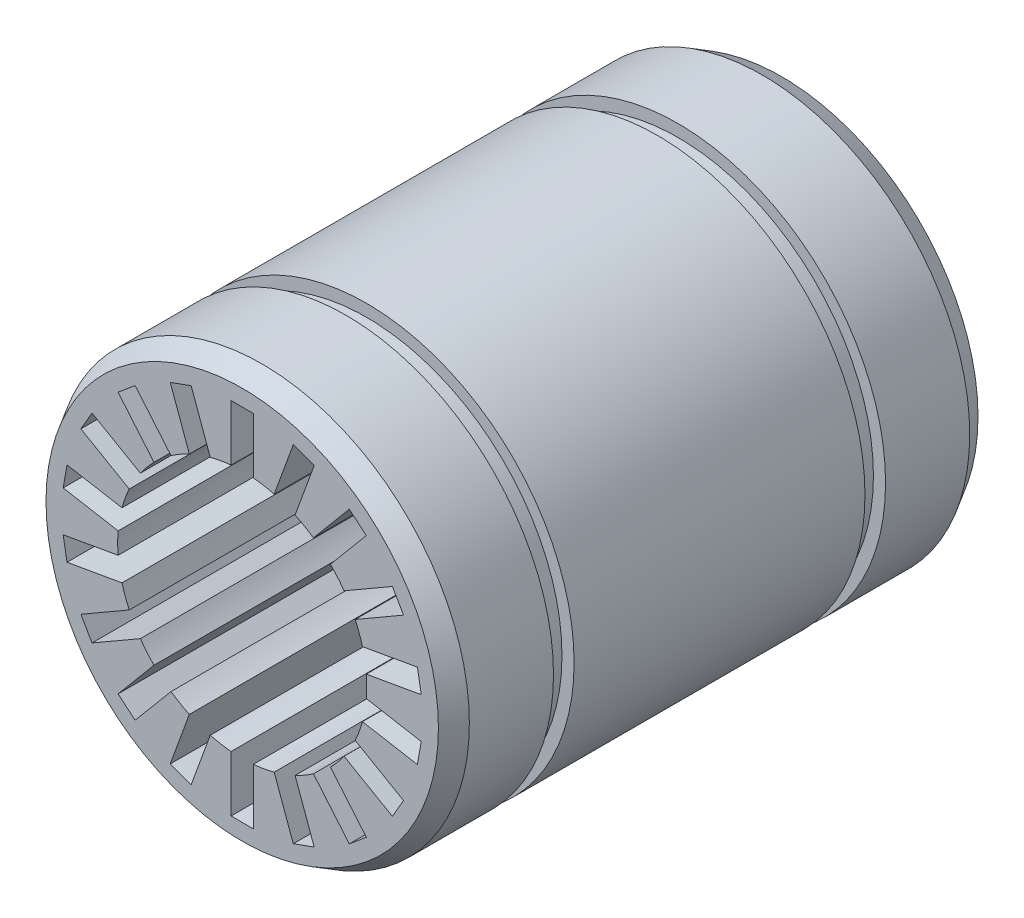
SolidWorks part; units mm, degrees
ref_plane "Front" through (0, 0, 0) normal (0, 0, 1) x (1, 0, 0)
ref_plane "Top" through (0, 0, 0) normal (0, 1, 0) x (1, 0, 0)
ref_plane "Right" through (0, 0, 0) normal (1, 0, 0) x (0, 0, -1)
sketch "Sketch1" plane through (0, 0, 0) normal (1, 0, 0) x (0, 0, -1)
  line L0 (-20.6375, 0) -> (20.6375, 0)
  line L1 (-20.6375, 0) -> (-20.6375, -15.875)
  line L2 (0, 0) -> (0, -15.875) construction
  line L3 (-20.6375, -15.875) -> (-12.7, -15.875)
  line L4 (-12.7, -15.875) -> (-12.7, -14.9479)
  line L5 (-12.7, -14.9479) -> (-11.1252, -14.9479)
  line L6 (-11.1252, -14.9479) -> (-11.1252, -15.875)
  line L7 (-20.6375, -15.875) -> (-20.6375, 15.875) construction
  line L8 (12.7, -14.9479) -> (20.6375, -14.9479) construction
  line L9 (20.6375, -14.9479) -> (20.6375, 14.9479) construction
  line L10 (-12.7, -15.875) -> (12.7, -15.875) construction
  line L11 (-11.1252, -15.875) -> (11.1252, -15.875)
  line L16 (11.1252, -14.9479) -> (11.1252, -15.875)
  line L17 (12.7, -14.9479) -> (11.1252, -14.9479)
  line L18 (12.7, -15.875) -> (12.7, -14.9479)
  line L19 (20.6375, -15.875) -> (12.7, -15.875)
  line L20 (20.6375, 0) -> (20.6375, -15.875)
  line L26 (-20.6375, 15.875) -> (20.6375, 15.875) construction
  line L27 (-11.9126, -14.9479) -> (-11.9126, 0) construction
  line L28 (-11.9126, -14.9479) -> (-11.9126, 14.9479) construction
  point P13 (20.6375, 15.875)
  dimension "Overall Lg B" = 41.275
  dimension "Lg C" = 25.4
  dimension "OD A" = 31.75
  dimension "Supplier dn Ret Ring Dia" = 29.8958
  dimension "Supplier S Groove Wd" = 1.5748
revolve "Bearing" add sketch "Sketch1" angle 360 mid plane about L0
sketch "Sketch2" plane through (0, 0, 0) normal (0, 0, 1) x (1, 0, 0)
  line L0 (-15.875, 0) -> (-13.7583, 0) construction
  line L1 (-13.7583, 0) -> (-11.6417, 0) construction
  line L2 (-11.6417, 0) -> (-9.525, 0) construction
  circle A0 centre (0, 0) radius 9.525
  circle A1 centre (0, 0) radius 15.875 construction
  circle A2 centre (0, 0) radius 13.7583 construction
  circle A3 centre (0, 0) radius 15.875 construction
  dimension "For Shaft Dia" = 19.05
extrude "Bore" cut sketch "Sketch2" against normal through all and the other way through all
sketch "Sketch3" plane through (0, 0, 0) normal (0, 0, 1) x (1, 0, 0)
  line L0 (0, -15.875) -> (0, 15.875) construction
  line L1 (-0.8509, 9.4869) -> (0.8509, 9.4869)
  line L2 (-0.8509, 9.4869) -> (-0.8509, 13.7583)
  line L3 (-0.8509, 13.7583) -> (0.8509, 13.7583)
  line L4 (0.8509, 9.4869) -> (0.8509, 13.7583)
  line L5 (-0.8509, 9.4869) -> (0.8509, 13.7583) construction
  line L6 (-0.8509, 13.7583) -> (0.8509, 9.4869) construction
  line L7 (0, 9.4869) -> (0, 13.7583) construction
  circle A0 centre (0, 0) radius 9.525 construction
  circle A1 centre (0, 0) radius 13.7583 construction
  point P0 (0, 11.6226)
  dimension "Pattern Groove Wd" = 1.7018
extrude "Ridge" cut sketch "Sketch3" against normal through all and the other way through all
pattern_circular "Ridge Pattern" count 18 over 360 about axis through (0, 0, 20.6375) along (0, 0, 1) of "Ridge" reverse direction yes
chamfer "OD Chamfer" distance 1.5 angle 30 2 edges at (15.875, 0, -20.6375) (15.875, 0, 20.6375) first distance on face at (15.875, 0, -20.6375) first distance on face at (15.875, 0, 12.7)
sketch "Sketch4" plane through (0, 0, 20.6375) normal (0, 0, 1) x (1, 0, 0)
  line L0 (-9.525, 0) -> (9.525, 0) construction
  circle A1 centre (0, 0) radius 9.525
  arc A2 (-0.8509, 9.4869) -> (-2.4451, 9.2058) centre (0, 0) ccw construction
ref_axis "Center Axis 1" through (0, 0, -20.6375) along (0, 0, 1)
